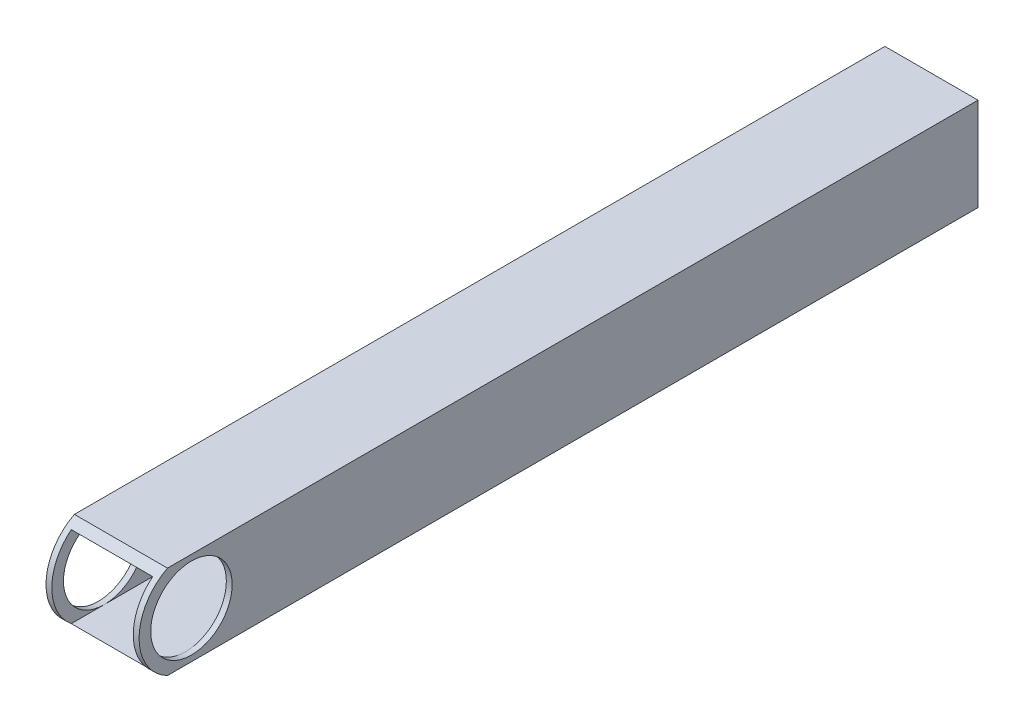
SolidWorks part; units mm, degrees
material "6061 Alloy"
ref_plane "Front Plane" through (0, 0, 0) normal (0, 0, 1) x (1, 0, 0)
ref_plane "Top Plane" through (0, 0, 0) normal (0, 1, 0) x (1, 0, 0)
ref_plane "Right Plane" through (0, 0, 0) normal (1, 0, 0) x (0, 0, -1)
sketch "Sketch1" plane through (0, 0, 0) normal (0, 0, 1) x (1, 0, 0)
  line L1 (12.7, -12.7) -> (-12.7, -12.7)
  line L2 (12.7, -12.7) -> (12.7, 12.7)
  line L3 (12.7, 12.7) -> (-12.7, 12.7)
  line L4 (-12.7, -12.7) -> (-12.7, 12.7)
  line L5 (12.7, -12.7) -> (-12.7, 12.7) construction
  line L6 (12.7, 12.7) -> (-12.7, -12.7) construction
  point P0 (0, 0)
  dimension "D1" = 25.4
extrude "Extrude-Thin1" add sketch "Sketch1" along normal mid plane 233.68 thin thin type one direction reverse wall 1.5875
sketch "Sketch2" plane through (12.7, 0, 0) normal (1, 0, 0) x (0, 0, -1)
  line L0 (-116.84, -12.7) -> (-116.84, 12.7) construction
  line L1 (-116.84, -12.7) -> (116.84, -12.7) construction
  circle A0 centre (-97.79, 0) radius 11.1125
  dimension "D1" = 22.225
  dimension "D2" = 19.05
  dimension "D3" = 12.7
extrude "Cut-Extrude1" cut sketch "Sketch2" against normal through all
sketch "Sketch3" plane through (12.7, 0, 0) normal (1, 0, 0) x (0, 0, -1)
  line L0 (-97.79, 14.2875) -> (-116.84, 14.2875)
  line L3 (-116.84, 14.2875) -> (-116.84, -12.7)
  line L4 (-116.84, -12.7) -> (-104.3354, -12.7)
  arc A0 (-97.79, 14.2875) -> (-104.3354, -12.7) centre (-97.79, 0) ccw
  circle A1 centre (-97.79, 0) radius 11.1125 construction
  dimension "D1" = 3.175
extrude "Cut-Extrude2" cut sketch "Sketch3" against normal through all
